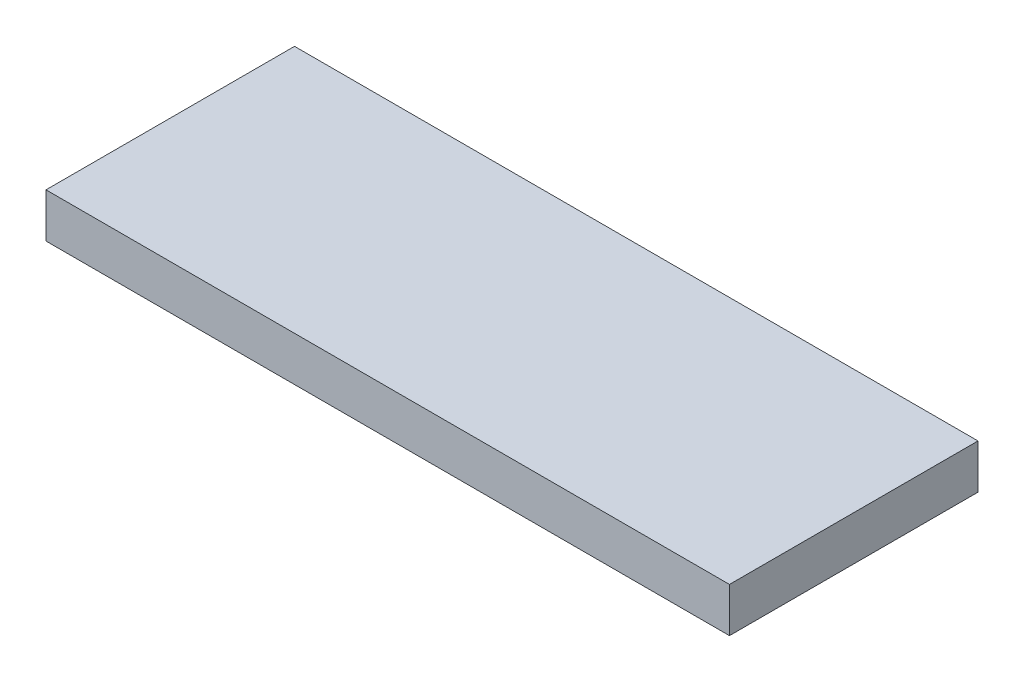
SolidWorks part; units mm, degrees
ref_plane "Front Plane" through (0, 0, 0) normal (0, 0, 1) x (1, 0, 0)
ref_plane "Top Plane" through (0, 0, 0) normal (0, 1, 0) x (1, 0, 0)
ref_plane "Right Plane" through (0, 0, 0) normal (1, 0, 0) x (0, 0, -1)
sketch "Sketch1" plane through (0, 0, 0) normal (0, 1, 0) x (1, 0, 0)
  line L1 (77, 28) -> (-77, 28)
  line L2 (77, 28) -> (77, -28)
  line L3 (77, -28) -> (-77, -28)
  line L4 (-77, 28) -> (-77, -28)
  line L5 (77, 28) -> (-77, -28) construction
  line L6 (77, -28) -> (-77, 28) construction
  point P0 (0, 0)
  dimension "D1" = 154
  dimension "D2" = 56
extrude "base" add sketch "Sketch1" along normal blind 10 contours L1 L4 L3 L2
sketch "Sketch2" plane through (0, 0, 0) normal (0, -1, 0) x (1, 0, 0)
  circle A0 centre (0, 0) radius 5.8
  dimension "D1" = 11.6
extrude "load cell button cut" cut sketch "Sketch2" against normal blind 5.2
equation "\"D2@Sketch1\"=46+10"
equation "\"D1@Sketch1\"=144+10"
